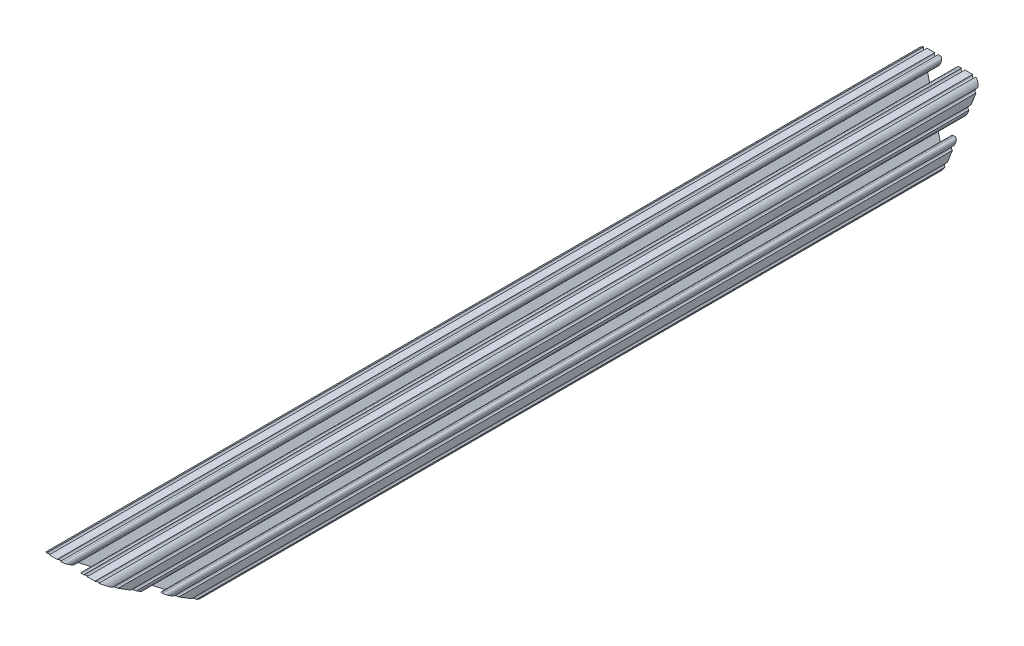
SolidWorks part; units mm, degrees
ref_plane "Front Plane" through (0, 0, 0) normal (0, 0, 1) x (1, 0, 0)
ref_plane "Top Plane" through (0, 0, 0) normal (0, 1, 0) x (1, 0, 0)
ref_plane "Right Plane" through (0, 0, 0) normal (1, 0, 0) x (0, 0, -1)
sketch "Sketch2" plane through (0, 0, 0) normal (0, 0, 1) x (1, 0, 0)
  line L0 (0, 19.05) -> (0, -19.05) construction
  line L1 (-19.05, 0) -> (19.05, 0) construction
  line L2 (4.064, -19.05) -> (19.05, -19.05)
  line L3 (19.05, -19.05) -> (19.05, -4.064)
  line L4 (4.064, -19.05) -> (4.064, -14.986)
  line L5 (4.064, -14.986) -> (12.1123, -14.986)
  line L6 (12.1123, -14.986) -> (4.1113, -6.985)
  line L7 (0, 0) -> (19.05, -19.05) construction
  line L8 (19.05, -4.064) -> (14.986, -4.064)
  line L9 (14.986, -4.064) -> (14.986, -12.1123)
  line L10 (14.986, -12.1123) -> (6.985, -4.1113)
  circle A0 centre (0, 0) radius 3.3274
  arc A1 (8.9963, -14.986) -> (9.909, -12.7826) centre (8.9963, -13.6953) ccw construction
  point P8 (0, -6.985)
  dimension "Center Hole Diameter" = 6.6548
  dimension "Rail Height" = 38.1
  dimension "Rail Width" = 38.1
  dimension "T-Slot Width" = 8.128
  dimension "Slot Inner Width" = 20.574
  dimension "Thickness" = 4.064
  dimension "Slot Depth" = 8.001
  dimension "D1" = 4.064
sketch "Sketch3" plane through (0, 0, 0) normal (1, 0, 0) x (0, 0, -1)
  line L0 (-342.5, -19.05) -> (342.5, -19.05) construction
  line L1 (-317.1, 0) -> (317.1, 0) construction
  dimension "Length" = 685
  dimension "D1" = 25.4
sketch "Sketch4" plane through (0, 0, 0) normal (0, 0, 1) x (1, 0, 0)
  line L0 (5.7912, -19.05) -> (14.3002, -19.05)
  line L1 (4.064, -19.05) -> (19.05, -19.05) construction
  line L2 (4.064, -19.05) -> (4.064, -14.986) construction
  line L3 (4.064, -14.986) -> (12.1123, -14.986) construction
  line L4 (4.064, -16.7132) -> (4.064, -17.3228)
  line L5 (5.7912, -14.986) -> (8.9963, -14.986)
  line L6 (0, -6.985) -> (2.833, -6.985)
  line L7 (12.1123, -14.986) -> (4.1113, -6.985) construction
  line L8 (5.0152, -7.8889) -> (9.909, -12.7826)
  line L9 (19.05, -19.05) -> (19.05, -4.064) construction
  line L10 (14.986, -12.1123) -> (6.985, -4.1113) construction
  line L11 (14.986, -4.064) -> (14.986, -12.1123) construction
  line L12 (14.986, -8.9963) -> (14.986, -5.7912)
  line L13 (19.05, -4.064) -> (14.986, -4.064) construction
  line L14 (16.7132, -4.064) -> (17.3228, -4.064)
  line L15 (19.05, -5.7912) -> (19.05, -14.3002)
  line L16 (12.7826, -9.909) -> (7.8889, -5.0152)
  line L17 (6.985, 0) -> (6.985, -2.833)
  line L18 (-19.05, 0) -> (19.05, 0) construction
  line L19 (0, -6.985) -> (0, -3.3274)
  line L20 (0, 19.05) -> (0, -19.05) construction
  line L21 (6.985, 0) -> (3.3274, 0)
  arc A0 (4.064, -17.3228) -> (5.7912, -19.05) centre (5.7912, -17.3228) ccw
  arc A2 (4.064, -16.7132) -> (5.7912, -14.986) centre (5.7912, -16.7132) cw
  arc A3 (8.9963, -14.986) -> (9.909, -12.7826) centre (8.9963, -13.6953) ccw
  arc A4 (2.833, -6.985) -> (5.0152, -7.8889) centre (2.833, -10.0711) cw
  arc A5 (14.3002, -19.05) -> (19.05, -14.3002) centre (14.3002, -14.3002) ccw
  arc A6 (12.7826, -9.909) -> (14.986, -8.9963) centre (13.6953, -8.9963) ccw
  arc A7 (14.986, -5.7912) -> (16.7132, -4.064) centre (16.7132, -5.7912) cw
  arc A8 (17.3228, -4.064) -> (19.05, -5.7912) centre (17.3228, -5.7912) cw
  arc A9 (7.8889, -5.0152) -> (6.985, -2.833) centre (10.0711, -2.833) cw
  circle A10 centre (0, 0) radius 3.3274 construction
  arc A11 (0, -3.3274) -> (3.3274, 0) centre (0, 0) ccw
  dimension "D1" = 4.7498
  dimension "D2" = 3.0861
  dimension "D3" = 1.7272
extrude "Boss-Extrude1" add sketch "Sketch4" along normal mid plane 685
sketch "Sketch5" plane through (0, 0, 0) normal (0, 0, 1) x (1, 0, 0)
  line L0 (4.064, -19.05) -> (19.05, -19.05) construction
  line L1 (5.7912, -14.986) -> (8.9963, -14.986) construction
  line L3 (0, 0) -> (19.05, -19.05) construction
  line L4 (8.9963, -14.986) -> (8.9963, -19.05) construction
  line L5 (12.1123, -14.986) -> (4.1113, -6.985) construction
  circle A0 centre (14.7395, -19.05) radius 1.016
  circle A1 centre (7.9803, -19.05) radius 1.016
  circle A2 centre (19.05, -14.7395) radius 1.016
  circle A3 centre (19.05, -7.9803) radius 1.016
  point P10 (7.3938, -14.986)
  point P12 (13.6953, -8.9963)
  dimension "D1" = 2.032
extrude "Cut-Extrude1" cut sketch "Sketch5" against normal through all both and the other way through all
mirror "Mirror1" about plane through (0, 0, 0) normal (1, 0, 0) of bodies 137 134
mirror "Mirror2" about plane through (0, 0, 0) normal (0, 1, 0) of bodies 135
sketch "Sketch6" plane through (19.05, 0, 0) normal (1, 0, 0) x (0, 0, -1)
  line L0 (-342.5, -18.034) -> (-342.5, -19.05) construction
  line L1 (-342.5, -15.7312) -> (-342.5, -18.8293) construction
  line L2 (-342.5, -13.7235) -> (-342.5, -15.7312) construction
  line L3 (-342.5, 15.7312) -> (-342.5, 13.7235) construction
  line L4 (-342.5, 18.8293) -> (-342.5, 15.7312) construction
  line L5 (-342.5, 19.05) -> (-342.5, 18.034) construction
  line L6 (-342.5, -18.034) -> (-342.5, -19.05)
  line L7 (-342.5, -15.7312) -> (-342.5, -18.8293)
  line L8 (-342.5, -13.7235) -> (-342.5, -15.7312)
  line L9 (-342.5, 15.7312) -> (-342.5, 13.7235)
  line L10 (-342.5, 18.8293) -> (-342.5, 15.7312)
  line L11 (-342.5, 19.05) -> (-342.5, 18.034)
  line L12 (-281.2898, -19.05) -> (-342.5, -19.05)
  line L13 (-342.5, 13.7235) -> (-342.5, -13.7235)
  line L14 (170.7848, -19.05) -> (160.7848, -19.05)
  line L15 (-342.5, 19.05) -> (-339.1205, 16.9465)
  line L16 (-339.1205, 16.9465) -> (-281.2898, -19.05)
  line L17 (184.5, 19.05) -> (160.7848, -19.05)
  line L18 (342.5, -19.05) -> (-342.5, -19.05) construction
  line L19 (342.5, -19.05) -> (170.7848, -19.05)
  line L20 (342.5, -19.05) -> (342.5, -18.034) construction
  line L21 (342.5, -18.8293) -> (342.5, -15.7312) construction
  line L22 (342.5, -15.7312) -> (342.5, -13.7235) construction
  line L23 (342.5, -13.7235) -> (342.5, -8.9963) construction
  line L24 (342.5, 13.7235) -> (342.5, 8.9963) construction
  line L25 (342.5, 13.7235) -> (342.5, 15.7312) construction
  line L26 (342.5, 15.7312) -> (342.5, 18.8293) construction
  line L27 (342.5, 18.034) -> (342.5, 19.05) construction
  line L28 (342.5, -19.05) -> (342.5, -18.034)
  line L29 (342.5, -18.8293) -> (342.5, -15.7312)
  line L30 (342.5, -15.7312) -> (342.5, -13.7235)
  line L31 (342.5, -13.7235) -> (342.5, -8.9963)
  line L32 (342.5, 13.7235) -> (342.5, 8.9963)
  line L33 (342.5, 13.7235) -> (342.5, 15.7312)
  line L34 (342.5, 15.7312) -> (342.5, 18.8293)
  line L35 (342.5, 18.034) -> (342.5, 19.05)
  line L36 (342.5, -8.9963) -> (342.5, 8.9963)
  line L37 (342.5, 19.05) -> (194.5, 19.05)
  line L38 (184.5, 19.05) -> (194.5, 19.05)
  line M4 (342.5, 8.9963) -> (342.5, 13.7235)
  line M5 (342.5, 13.7235) -> (-342.5, 13.7235)
  line M6 (-342.5, 13.7235) -> (-342.5, 8.9963)
  line M7 (-342.5, 8.9963) -> (342.5, 8.9963)
extrude "Cut-Extrude2" cut sketch "Sketch6" against normal through all contours L16 L13 L8 L7 L6 L12 M7 | L31 L36 L17 L19 L28 L29 L30 M7 | L35 L37 L17 L33 L34 M5 | L17 M5 M7 M4 | L16 M5 M6 M7 | L16 L15 L11 L10 L9 M5 region at (19.05, -7.7494, 320.9725) region at (19.05, 11.1177, 336.1281) region at (19.05, 15.499, 339.6475) region at (19.05, -5.2627, -255.9333) region at (19.05, 11.3528, -261.1044) region at (19.05, 16.3775, -262.6683)
equation "\"D1@Boss-Extrude1\"=\"Length@Sketch3\""
equation "\"D1@Sketch2\"=\"Thickness@Sketch2\""
equation "\"D2@Sketch4\"=\"Slot Inner Width@Sketch2\"*0.15"
equation "\"D1@Sketch4\"=\"D3@Sketch4\"*2.75"
equation "\"D3@Sketch4\"=\"Thickness@Sketch2\"*0.425"
equation "\"D1@Sketch5\"=\"Thickness@Sketch2\"*0.5"
